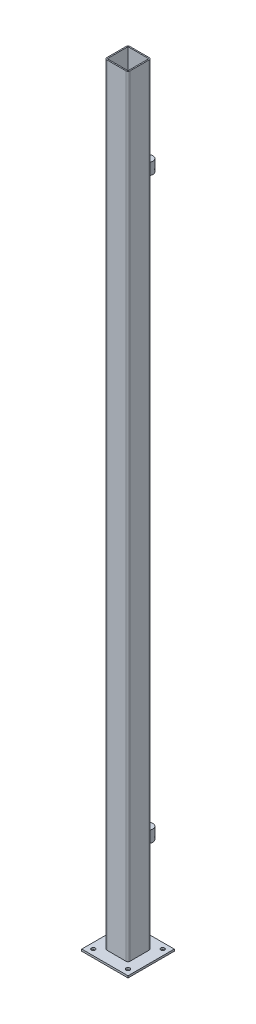
SolidWorks part; units mm, degrees
ref_plane "前视" through (0, 0, 0) normal (0, 0, 1) x (1, 0, 0)
ref_plane "上视" through (0, 0, 0) normal (0, 1, 0) x (1, 0, 0)
ref_plane "右视" through (0, 0, 0) normal (1, 0, 0) x (0, 0, -1)
sketch "草图1" plane through (0, 0, 0) normal (0, 1, 0) x (1, 0, 0)
  line L0 (0, 0) -> (0, 57.1093) construction
  line L1 (-60, 60) -> (60, 60)
  line L2 (-60, 60) -> (-60, -60)
  line L3 (-60, -60) -> (60, -60)
  line L4 (60, 60) -> (60, -60)
  line L5 (0, 0) -> (82.0444, 0) construction
  dimension "D1" = 120
  dimension "D2" = 120
extrude "凸台-拉伸1" add sketch "草图1" along normal blind 5
sketch "草图2" plane through (0, 5, 0) normal (0, 1, 0) x (1, 0, 0)
  line L13 (-30, 60) -> (-30, -60)
  line L14 (-30, 30) -> (-30, -30)
  line L20 (27, 27) -> (-27, 27)
  line L21 (-27, 27) -> (-27, -27)
  line L22 (-27, -27) -> (27, -27)
  line L23 (-60, -30) -> (30, -30)
  line L24 (30, -30) -> (30, 30)
  line L25 (30, 30) -> (-60, 30)
  line L26 (-30, -30) -> (30, -30)
  line L27 (30, -30) -> (30, 30)
  line L28 (30, 30) -> (-30, 30)
  line L29 (27, -27) -> (27, 27)
  dimension "D1" = 30
  dimension "D2" = 30
  dimension "D3" = 3
extrude "凸台-拉伸2" add sketch "草图2" along normal blind 2000
fillet "圆角1" radius 5 4 edges at (-30, 1005, 30) (30, 1005, 30) (-30, 1005, -30) (30, 1005, -30)
sketch "草图3" plane through (0, 5, 0) normal (0, 1, 0) x (1, 0, 0)
  circle A0 centre (-45, 45) radius 5
  circle A1 centre (45, 45) radius 5
  circle A2 centre (-45, -45) radius 5
  circle A3 centre (45, -45) radius 5
  dimension "D1" = 10
  dimension "D2" = 90
  dimension "D3" = 45
  dimension "D4" = 90
  dimension "D5" = 45
extrude "切除-拉伸1" cut sketch "草图3" against normal blind 2000
ref_plane "基准面1" through (0, 0, 0) normal (1, 0, 0) x (0, 0, -1)
sketch "草图6" plane through (0, 0, 0) normal (1, 0, 0) x (0, 0, -1)
  line L0 (30, 2005) -> (30, 5) construction
  line L1 (30, 1785) -> (30, 1725)
  line L2 (30, 1785) -> (33, 1785)
  line L3 (33, 1785) -> (33, 1755)
  line L4 (33, 1755) -> (40, 1755)
  line L5 (40, 1755) -> (40, 1725)
  line L6 (40, 1725) -> (30, 1725)
  line L7 (-25, 2005) -> (25, 2005) construction
  dimension "D1" = 30
  dimension "D2" = 60
  dimension "D3" = 10
  dimension "D4" = 3
  dimension "D5" = 220
extrude "凸台-拉伸5" add sketch "草图6" along normal mid plane 15
pattern_linear "阵列(线性)1" count 2 spacing 1500 along (0, -1, 0) of "凸台-拉伸5"
sketch "草图7" plane through (0, 1755, 0) normal (0, 1, 0) x (1, 0, 0)
  line L0 (7.5, 40) -> (-7.5, 40) construction
  circle A0 centre (0, 52) radius 12.5
  dimension "D1" = 25
  dimension "D2" = 12
extrude "凸台-拉伸6" add sketch "草图7" against normal blind 30
sketch "草图8" plane through (0, 1755, 0) normal (0, 1, 0) x (1, 0, 0)
  circle A0 centre (0, 50) radius 4
  arc A1 (3.5, 40) -> (-3.5, 40) centre (0, 52) ccw construction
  dimension "D2" = 8
  dimension "D1" = 2
extrude "凸台-拉伸7" add sketch "草图8" along normal blind 35
pattern_linear "阵列(线性)2" count 2 spacing 1500 along (0, -1, 0) of "凸台-拉伸7", "凸台-拉伸6"
ref_plane "基准面2" through (0, 0, 0) normal (-1, 0, 0) x (0, 0, 1)
ref_plane "基准面3" through (0, 0, 0) normal (0, 0, 1) x (1, 0, 0)
ref_axis "基准轴1" through (0, 2105, 0) along (0, -1, 0)
